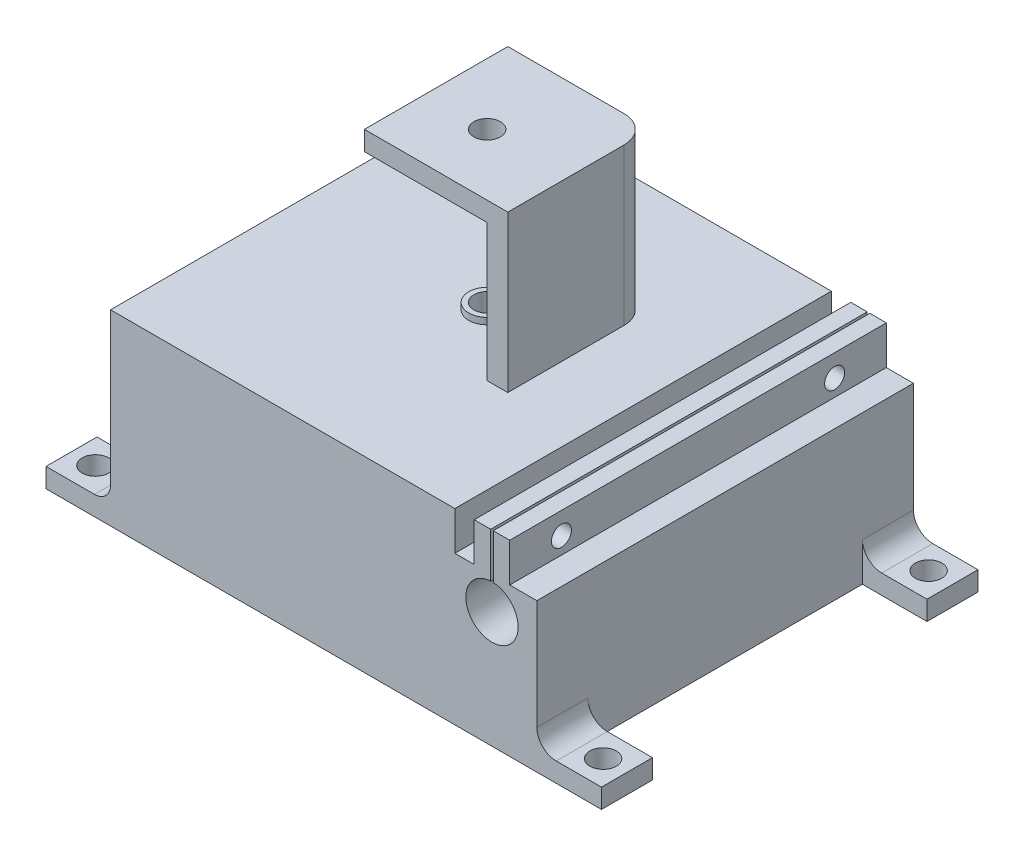
SolidWorks part; units mm, degrees
ref_plane "Спереди" through (0, 0, 0) normal (0, 0, 1) x (1, 0, 0)
ref_plane "Сверху" through (0, 0, 0) normal (0, 1, 0) x (1, 0, 0)
ref_plane "Справа" through (0, 0, 0) normal (1, 0, 0) x (0, 0, -1)
other "Configuration Table"
sketch "Sketch1" plane through (0, 0, 0) normal (0, 1, 0) x (1, 0, 0)
  line L0 (-33, 29.15) -> (-3.85, 29.15) construction
  line L1 (-33, -29.15) -> (33, -29.15)
  line L2 (-33, -29.15) -> (-33, 29.15)
  line L3 (-33, 29.15) -> (33, 29.15)
  line L4 (33, -29.15) -> (33, 29.15)
  line L5 (-33, -29.15) -> (33, 29.15) construction
  line L6 (-33, 29.15) -> (33, -29.15) construction
  line L7 (-3.85, 29.15) -> (-3.85, 0) construction
  circle A1 centre (-3.85, 0) radius 2.05
  point P0 (0, 0)
  dimension "D5" = 4.1
  dimension "D1" = 66
  dimension "D2" = 58.3
  dimension "D3" = 29.15
  dimension "D4" = 29.15
extrude "Boss-Extrude1" add sketch "Sketch1" along normal blind 29
sketch "Sketch3" plane through (0, 29, 0) normal (0, 1, 0) x (1, 0, 0)
  line L0 (-33, 21.25) -> (-33, -21.25)
  line L1 (-33, 29.15) -> (-33, -29.15) construction
  line L2 (-33, -21.25) -> (17.4, -21.25)
  line L4 (-33, -29.15) -> (33, -29.15) construction
  line L6 (17.4, -21.25) -> (17.4, 21.25)
  line L7 (33, 29.15) -> (-33, 29.15) construction
  line L10 (-25.1, 21.25) -> (-33, 21.25)
  line L11 (-25.1, 21.25) -> (17.4, 21.25)
  dimension "D1" = 7.9
  dimension "D2" = 50.4
  dimension "D3" = 7.9
extrude "Cut-Extrude1" cut sketch "Sketch3" along normal blind 20 from surface starting at face at (0, 0, 0)
sketch "Sketch6" plane through (0, 0, 0) normal (0, -1, 0) x (1, 0, 0)
  line L0 (-33, 29.15) -> (-33, 21.25)
  line L1 (-33, 29.15) -> (-43, 29.15)
  line L2 (-33, 21.25) -> (-43, 21.25)
  line L3 (-43, 29.15) -> (-43, 21.25)
  line L4 (-33, -21.25) -> (-33, -29.15)
  line L5 (-33, -21.25) -> (-43, -21.25)
  line L6 (-33, -29.15) -> (-43, -29.15)
  line L7 (-43, -21.25) -> (-43, -29.15)
  line L8 (33, 29.15) -> (33, 21.25)
  line L9 (33, 29.15) -> (43, 29.15)
  line L10 (33, 21.25) -> (43, 21.25)
  line L11 (43, 29.15) -> (43, 21.25)
  line L12 (33, 29.15) -> (33, -29.15) construction
  line L13 (33, -21.25) -> (33, -29.15)
  line L14 (33, -21.25) -> (43, -21.25)
  line L15 (33, -29.15) -> (43, -29.15)
  line L16 (43, -21.25) -> (43, -29.15)
  line L17 (-38, -21.25) -> (-38, -29.15) construction
  line L18 (-38, 29.15) -> (-38, 21.25) construction
  line L19 (38, 29.15) -> (38, 21.25) construction
  line L20 (38, -21.25) -> (38, -29.15) construction
  circle A0 centre (-39.3, -25.2) radius 2.05
  circle A1 centre (-39.3, 25.2) radius 2.05
  circle A2 centre (39.3, 25.2) radius 2.05
  circle A3 centre (39.3, -25.2) radius 2.05
  dimension "D9" = 4.1
  dimension "D10" = 3.7
  dimension "D1" = 10
  dimension "D2" = 7.9
  dimension "D3" = 10
  dimension "D4" = 10
  dimension "D5" = 10
  dimension "D6" = 7.9
  dimension "D7" = 7.9
  dimension "D8" = 7.9
  dimension "D11" = 3.7
  dimension "D12" = 3.7
  dimension "D13" = 3.7
  dimension "D14" = 3.7
extrude "Boss-Extrude2" add sketch "Sketch6" against normal blind 3
sketch "Sketch7" plane through (0, 0, -29.15) normal (0, 0, -1) x (-1, 0, 0)
  line L0 (-33, 7) -> (-33, 6)
  line L1 (-33, 29) -> (-33, 3) construction
  line L2 (-36, 3) -> (-37, 3)
  line L3 (-33, 3) -> (-43, 3) construction
  line L4 (33, 7) -> (33, 5.5)
  line L5 (33, 29) -> (33, 3) construction
  line L6 (43, 3) -> (33, 3) construction
  line L7 (35.5, 3) -> (37, 3)
  line L8 (-36, 3) -> (-33, 3)
  line L9 (-33, 3) -> (-33, 6)
  line L10 (-36, 3) -> (-33, 3)
  line L11 (-33, 3) -> (-33, 6)
  line L12 (-36, 3) -> (-36, 2.3913)
  line L13 (33, 5.5) -> (33, 3)
  line L14 (33, 3) -> (35.5, 3)
  arc A0 (-33, 6) -> (-36, 3) centre (-36, 6) cw
  arc A1 (35.5, 3) -> (33, 5.5) centre (35.5, 5.5) cw
  point P10 (-33, 3)
  point P20 (33, 3)
  line M8 (43, 3) -> (33, 3)
  line M9 (33, 3) -> (33, 29)
  line M11 (-33, 29) -> (-33, 3)
  line M12 (-33, 3) -> (-43, 3)
  dimension "D3" = 3
  dimension "D6" = 2.5
  dimension "D1" = 4
  dimension "D2" = 4
  dimension "D4" = 4
  dimension "D5" = 4
extrude "Boss-Extrude4" add sketch "Sketch7" against normal up to surface (7.9 mm away) contours A1 M8 M9 | A0 M11 M12 region at (33.6701, 3.6701, -29.15) region at (-33.5584, 3.5584, -29.15) up to face at (38, 1.5, -21.25)
extrude "Boss-Extrude5" add sketch "Sketch7<5>" along normal up to surface (-50.4 mm away) from surface contours A1 M8 M9 | A0 M11 M12 region at (33.6701, 3.6701, -29.15) region at (-33.5584, 3.5584, -29.15) up to face at (-19.5333, 7.6667, 21.25) starting at face at (0, 8.75, 29.15)
sketch "Sketch7<5>" plane through (0, 0, -29.15) normal (0, 0, -1) x (-1, 0, 0) same geometry as "Sketch7"
sketch "Sketch8" plane through (0, 0, 29.15) normal (0, 0, 1) x (1, 0, 0)
  line L0 (17.4, 0) -> (26.05, 0) construction
  line L1 (-43, 0) -> (43, 0) construction
  line L2 (26.05, 0) -> (26.05, 18) construction
  line L3 (33, 29) -> (33, 6) construction
  circle A0 centre (26.05, 18) radius 4.05
  dimension "D3" = 8.1
  dimension "D1" = 6.95
  dimension "D2" = 18
extrude "Cut-Extrude4" cut sketch "Sketch8" along normal up to next from surface starting at face at (0.0396, 8.0361, -29.15)
sketch "Sketch10" plane through (0, 0, -29.15) normal (0, 0, -1) x (-1, 0, 0)
  line L0 (-33, 29) -> (-28.8, 29) construction
  line L1 (-33, 29) -> (33, 29) construction
  line L2 (-28.8, 29) -> (-23.3, 29) construction
  line L3 (-26.05, 18) -> (-22, 18) construction
  line L4 (-17.4, 20) -> (-17.4, 0) construction
  line L5 (-23.3, 23) -> (-23.3, 25.6) construction
  line L6 (-23.3, 29) -> (-20.3, 29)
  line L7 (-23.3, 29) -> (-23.3, 23)
  line L8 (-23.3, 23) -> (-20.3, 23)
  line L9 (-20.3, 29) -> (-20.3, 23)
  line L10 (-33, 29) -> (-33, 6) construction
  line L11 (-28.8, 29) -> (-33, 29)
  line L12 (-28.8, 29) -> (-28.8, 23)
  line L13 (-28.8, 23) -> (-33, 23)
  line L14 (-33, 29) -> (-33, 23)
  line L15 (-23.3, 23) -> (-23.3, 28.2) construction
  line L16 (-23.3, 23) -> (-23.3, 25.6) construction
  line L17 (-23.3, 25.6) -> (-28.8, 25.6) construction
  line L19 (-26.05, 29) -> (-26.05, 23) construction
  line L20 (-26.05, 18) -> (-26.05, 29) construction
  line L21 (-26.25, 29) -> (-25.85, 29)
  line L22 (-26.25, 29) -> (-26.25, 21.3825)
  line L23 (-26.25, 21.3825) -> (-25.85, 21.3825)
  line L24 (-25.85, 29) -> (-25.85, 21.3825)
  circle A0 centre (-26.05, 18) radius 4.05 construction
  dimension "D8" = 0.2
  dimension "D1" = 9.7
  dimension "D2" = 3
  dimension "D3" = 5.5
  dimension "D4" = 6
  dimension "D5" = 2.9
  dimension "D6" = 2.6
  dimension "D7" = 4.2
  dimension "D9" = 0.2
  dimension "D10" = 2.55
  dimension "D11" = 2.55
extrude "Cut-Extrude5" cut sketch "Sketch10" against normal up to next
sketch "Sketch11" plane through (28.8, 0, 0) normal (1, 0, 0) x (0, 0, -1)
  line L0 (-29.15, 23) -> (-21.15, 23) construction
  line L1 (-29.15, 23) -> (29.15, 23) construction
  line L2 (-21.15, 23) -> (-21.15, 25.6) construction
  line L3 (0, 29) -> (0, 23) construction
  line L4 (-29.15, 29) -> (29.15, 29) construction
  circle A0 centre (-21.15, 25.6) radius 1.55
  circle A1 centre (21.15, 25.6) radius 1.55
  dimension "D3" = 3.1
  dimension "D1" = 8
  dimension "D2" = 2.6
extrude "Cut-Extrude6" cut sketch "Sketch11" against normal up to surface (5.5 mm away) up to face at (23.3, 26, 0)
sketch "Sketch12" plane through (0, 20, 0) normal (0, -1, 0) x (1, 0, 0)
  line L1 (-7.95, 0) -> (-5.9, -3.5507)
  line L2 (-5.9, -3.5507) -> (-1.8, -3.5507)
  line L3 (-1.8, -3.5507) -> (0.25, 0)
  line L4 (0.25, 0) -> (-1.8, 3.5507)
  line L5 (-1.8, 3.5507) -> (-5.9, 3.5507)
  line L6 (-5.9, 3.5507) -> (-7.95, 0)
  circle A0 centre (-3.85, 0) radius 3.5507 construction
  dimension "D1" = 8.2
extrude "Cut-Extrude7" cut sketch "Sketch12" against normal blind 2.5
sketch "Sketch13" plane through (0, 29, 0) normal (0, 1, 0) x (1, 0, 0)
  line L0 (-3.85, 0) -> (-3.85, 9.5) construction
  line L1 (-3.85, 0) -> (5.65, 0) construction
  line L2 (-3.85, 9.5) -> (-13.35, 9.5) construction
  line L3 (5.65, 0) -> (5.65, -9.5) construction
  line L4 (-13.35, 9.5) -> (-13.35, 12.7)
  line L5 (-13.35, 12.7) -> (4.65, 12.7)
  line L6 (8.85, 8.5) -> (8.85, -9.5)
  line L7 (8.85, -9.5) -> (5.65, -9.5)
  line L8 (5.65, -9.5) -> (5.65, 6.3)
  line L9 (2.45, 9.5) -> (-13.35, 9.5)
  arc A0 (5.65, 6.3) -> (2.45, 9.5) centre (2.45, 6.3) ccw
  arc A1 (8.85, 8.5) -> (4.65, 12.7) centre (4.65, 8.5) ccw
  point P15 (8.85, 12.7)
  dimension "D1" = 3.2
  dimension "D6" = 3.2
  dimension "D7" = 4.2
  dimension "D2" = 9.5
  dimension "D3" = 3.2
  dimension "D4" = 22.2
  dimension "D5" = 22.2
extrude "Boss-Extrude6" add sketch "Sketch13" along normal blind 21.2
sketch "Sketch14" plane through (0, 50.2, 0) normal (0, 1, 0) x (1, 0, 0)
  line L1 (-13.35, 12.7) -> (4.65, 12.7)
  line L2 (-13.35, 12.7) -> (-13.35, -9.5)
  line L3 (-13.35, -9.5) -> (8.85, -9.5)
  line L4 (8.85, 8.5) -> (8.85, -9.5)
  circle A0 centre (-3.85, 0) radius 2.05
  arc A1 (8.85, 8.5) -> (4.65, 12.7) centre (4.65, 8.5) ccw
  dimension "D1" = 4.1
  dimension "D2" = 4.2
extrude "Boss-Extrude7" add sketch "Sketch14" along normal blind 3
sketch "Sketch15" plane through (0, 53.2, 0) normal (0, 1, 0) x (1, 0, 0)
  circle A0 centre (-3.85, 0) radius 2.85
  circle A1 centre (-3.85, 0) radius 2.05
  dimension "D1" = 4.1
  dimension "D2" = 0.8
extrude "Boss-Extrude8" add sketch "Sketch15" against normal blind 1 from surface starting at face at (-3.85, 50.2, 2.05)
extrude "Boss-Extrude9" add sketch "Sketch15<2>" along normal blind 1 from surface starting at face at (-6.35, 29, 0)
sketch "Sketch15<2>" plane through (0, 53.2, 0) normal (0, 1, 0) x (1, 0, 0) same geometry as "Sketch15"
